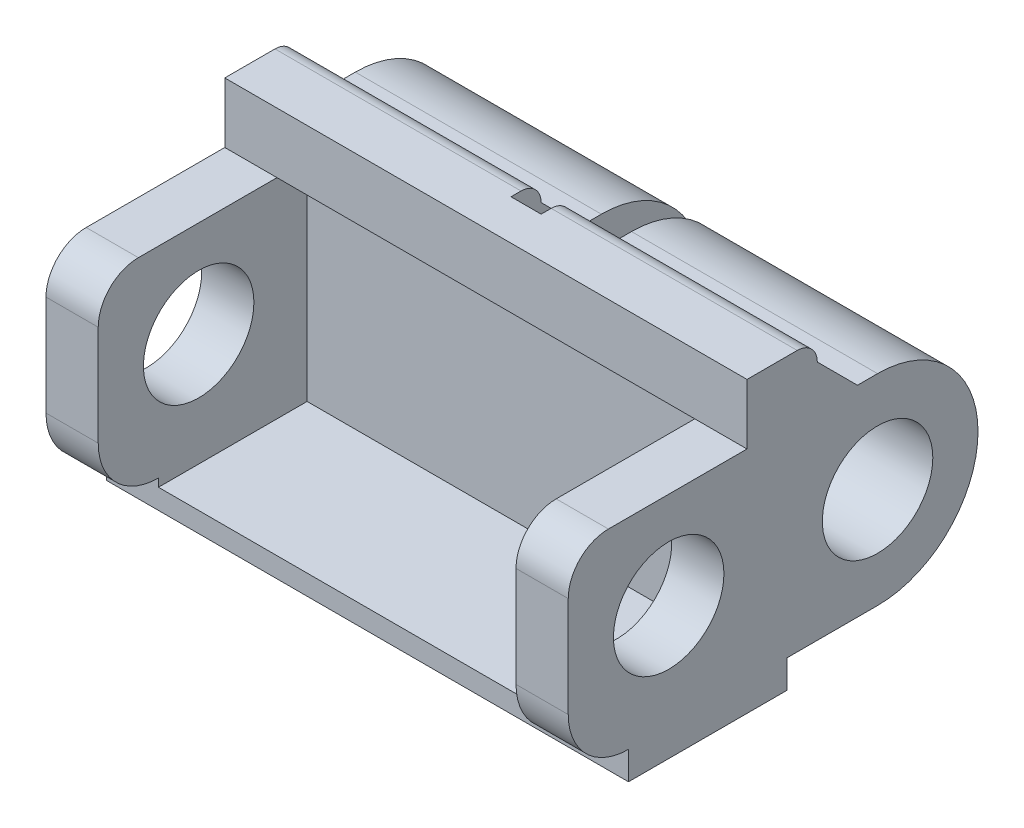
SolidWorks part; units mm, degrees
ref_plane "Front Plane" through (0, 0, 0) normal (0, 0, 1) x (1, 0, 0)
ref_plane "Top Plane" through (0, 0, 0) normal (0, 1, 0) x (1, 0, 0)
ref_plane "Right Plane" through (0, 0, 0) normal (1, 0, 0) x (0, 0, -1)
sketch "Sketch3" plane through (10, 0, 0) normal (1, 0, 0) x (0, 0, -1)
  line L1 (-42, 41.45) -> (-47, 41.45)
  line L2 (-47, 41.45) -> (-37, 41.45)
  line L4 (-44, 31.45) -> (-40, 31.45)
  line L5 (-37, 34.45) -> (-37, 41.85)
  line L6 (-37, 41.85) -> (-47, 41.85)
  line L7 (-47, 41.85) -> (-47, 34.45)
  line L8 (-44, 31.45) -> (-40, 31.45)
  line L9 (-37, 34.45) -> (-37, 41.45)
  line L11 (-47, 41.45) -> (-47, 34.45)
  circle A0 centre (-42, 36.65) radius 2.75
  arc A3 (-40, 31.45) -> (-37, 34.45) centre (-40, 34.45) ccw
  arc A4 (-47, 34.45) -> (-44, 31.45) centre (-44, 34.45) ccw
  arc A5 (-40, 31.45) -> (-37, 34.45) centre (-40, 34.45) ccw
  arc A6 (-47, 34.45) -> (-44, 31.45) centre (-44, 34.45) ccw
  circle M10 centre (-42, 36.65) radius 2.75
  line M11 (-44, 31.45) -> (-40, 31.45)
  arc M12 (-40, 31.45) -> (-37, 34.45) centre (-40, 34.45) ccw
  line M13 (-37, 34.45) -> (-37, 41.85)
  line M15 (-47, 41.85) -> (-47, 34.45)
  arc M16 (-47, 34.45) -> (-44, 31.45) centre (-44, 34.45) ccw
  dimension "D1" = 0
extrude "Boss-Extrude1" add sketch "Sketch3" along normal blind 3 contours L2 L1 M15 M16 M11 M12 M13 M10
sketch "Sketch4" plane through (-10, 0, 0) normal (-1, 0, 0) x (0, 0, 1)
  line L4 (47, 41.45) -> (37, 41.45)
  line L5 (47, 34.45) -> (47, 41.45)
  line L6 (40, 31.45) -> (44, 31.45)
  line L7 (37, 41.45) -> (37, 34.45)
  line L8 (47, 41.45) -> (37, 41.45)
  line L9 (47, 34.45) -> (47, 41.45)
  line L10 (40, 31.45) -> (44, 31.45)
  line L11 (37, 41.45) -> (37, 34.45)
  circle A1 centre (42, 36.65) radius 2.75
  circle A2 centre (42, 36.65) radius 2.75
  arc A4 (44, 31.45) -> (47, 34.45) centre (44, 34.45) ccw
  arc A5 (37, 34.45) -> (40, 31.45) centre (40, 34.45) ccw
  arc A6 (44, 31.45) -> (47, 34.45) centre (44, 34.45) ccw
  arc A7 (37, 34.45) -> (40, 31.45) centre (40, 34.45) ccw
  dimension "D1" = 0
  dimension "D2" = 0
extrude "Boss-Extrude2" add sketch "Sketch4" along normal blind 3 separate body
sketch "Sketch5" plane through (-13, 0, 0) normal (-1, 0, 0) x (0, 0, 1)
  line L0 (37, 41.45) -> (36.6, 41.45)
  line L1 (40, 31.45) -> (36.6, 31.45)
  line L2 (36.6, 41.45) -> (36.6, 31.45)
  line L3 (37, 41.45) -> (37, 34.45) construction
  line L4 (37, 41.45) -> (37, 34.45)
  arc A0 (37, 34.45) -> (40, 31.45) centre (40, 34.45) ccw construction
  arc A2 (37, 34.45) -> (40, 31.45) centre (40, 34.45) ccw
  dimension "D1" = 0.4
extrude "Boss-Extrude3" add sketch "Sketch5" against normal blind 3
sketch "Sketch6" plane through (13, 0, 0) normal (1, 0, 0) x (0, 0, -1)
  line L4 (-36.6, 31.45) -> (-36.6, 41.45)
  line L5 (-36.6, 41.45) -> (-47, 41.45)
  line L6 (-47, 41.45) -> (-47, 34.45)
  line L7 (-44, 31.45) -> (-36.6, 31.45)
  line L8 (-36.6, 31.45) -> (-36.6, 41.45)
  line L9 (-36.6, 41.45) -> (-47, 41.45)
  line L10 (-47, 41.45) -> (-47, 34.45)
  line L11 (-44, 31.45) -> (-36.6, 31.45)
  circle A0 centre (-42, 36.65) radius 2.75 construction
  arc A1 (-47, 34.45) -> (-44, 31.45) centre (-44, 34.45) ccw
  arc A2 (-47, 34.45) -> (-44, 31.45) centre (-44, 34.45) ccw
  circle A3 centre (-42, 36.65) radius 2.75
  dimension "D1" = 0
extrude "Boss-Extrude4" add sketch "Sketch6" against normal blind 3
sketch "Sketch7" plane through (-10, 0, 0) normal (1, 0, 0) x (0, 0, -1)
  line L4 (-36.6, 41.45) -> (-47, 41.45)
  line L5 (-47, 41.45) -> (-47, 34.45)
  line L6 (-44, 31.45) -> (-36.6, 31.45)
  line L7 (-36.6, 31.45) -> (-36.6, 41.45)
  line L8 (-36.6, 41.45) -> (-47, 41.45)
  line L9 (-47, 41.45) -> (-47, 34.45)
  line L10 (-44, 31.45) -> (-36.6, 31.45)
  line L11 (-36.6, 31.45) -> (-36.6, 41.45)
  arc A1 (-47, 34.45) -> (-44, 31.45) centre (-44, 34.45) ccw
  arc A2 (-47, 34.45) -> (-44, 31.45) centre (-44, 34.45) ccw
  dimension "D1" = 0
extrude "Cut-Extrude1" cut sketch "Sketch7" against normal blind 0.4
sketch "Sketch8" plane through (10, 0, 0) normal (-1, 0, 0) x (0, 0, 1)
  line L4 (47, 41.45) -> (36.6, 41.45)
  line L5 (36.6, 41.45) -> (36.6, 31.45)
  line L6 (36.6, 31.45) -> (44, 31.45)
  line L7 (47, 34.45) -> (47, 41.45)
  line L8 (47, 41.45) -> (36.6, 41.45)
  line L9 (36.6, 41.45) -> (36.6, 31.45)
  line L10 (36.6, 31.45) -> (44, 31.45)
  line L11 (47, 34.45) -> (47, 41.45)
  arc A1 (44, 31.45) -> (47, 34.45) centre (44, 34.45) ccw
  arc A2 (44, 31.45) -> (47, 34.45) centre (44, 34.45) ccw
  dimension "D1" = 0
extrude "Cut-Extrude2" cut sketch "Sketch8" against normal blind 0.4
sketch "Sketch9" plane through (13, 0, 0) normal (1, 0, 0) x (0, 0, -1)
  line L0 (-36.6, 31.45) -> (-34.3437, 31.45)
  line L1 (-36.6, 41.45) -> (-36.6, 31.45)
  line L2 (-36.6, 41.45) -> (-31.6, 41.45)
  line L4 (-31.6, 31.45) -> (-36.6, 31.45)
  line L5 (-36.6, 36.45) -> (-26.6, 36.45)
  circle A0 centre (-31.6, 36.45) radius 2.75
  circle A1 centre (-31.6, 36.45) radius 5
  line M9 (-36.6, 31.45) -> (-36.6, 41.45)
  dimension "D2" = 5.5
extrude "Boss-Extrude5" add sketch "Sketch9" against normal up to surface (26 mm away) contours L5 A1 A0 | L5 A1 A0 | A1 L2 L1 | A1 L0 L4 M9 up to face at (-13, 35.9257, 42.3643)
ref_plane "Plane1" through (0, 0, 26.6) normal (0, 0, 1) x (1, 0, 0)
sketch "Sketch11" plane through (0, 0, 26.6) normal (0, 0, 1) x (1, 0, 0)
  line L0 (-0.75, 41.85) -> (0.75, 41.85)
  line L1 (0.75, 41.85) -> (0.75, 31.45)
  line L2 (-10.4, 31.45) -> (10.4, 31.45) construction
  line L3 (0.75, 34.45) -> (0.75, 31.45) construction
  line L4 (0.75, 31.45) -> (-0.75, 31.45)
  line L5 (-0.75, 31.45) -> (-0.75, 34.45) construction
  line L6 (-0.75, 31.45) -> (-0.75, 41.85)
extrude "Cut-Extrude4" cut sketch "Sketch11" along normal mid plane 19
ref_plane "Plane2" through (0, 31.05, 0) normal (0, -1, 0) x (-1, 0, 0)
sketch "Sketch13" plane through (0, 31.05, 0) normal (0, -1, 0) x (-1, 0, 0)
  line L0 (-10.4, -36.6) -> (-13, -36.6)
  line L1 (-13, -44) -> (-13, -31.6) construction
  line L2 (-13, -36.6) -> (13, -36.6)
  line L3 (13, -31.6) -> (13, -44) construction
  line L4 (13, -36.6) -> (13, -41.6)
  line L5 (13, -41.6) -> (-13, -41.6)
  line L6 (-13, -41.6) -> (-13, -36.6)
  line L7 (-0.75, -36.1) -> (-0.75, -36.6)
  line L8 (-0.75, -36.1) -> (-13, -36.1)
  line L9 (-13, -36.1) -> (-13, -36.6)
  line L10 (-0.75, -36.1) -> (13, -36.1)
  line L11 (13, -36.1) -> (13, -36.6)
  dimension "D1" = 5
extrude "Boss-Extrude6" add sketch "Sketch13" along normal blind 1 separate body contours L6 L5 L4 L2 L0 | L11 L10 L7 L2 | L8 L9 L0 L2 L7
sketch "Sketch14" plane through (0, 31.45, 0) normal (0, -1, 0) x (1, 0, 0)
  line L0 (10.4, 41.6) -> (13, 41.6)
  line L1 (-13, 41.6) -> (13, 41.6) construction
  line L2 (10.4, 36.6) -> (10.4, 44) construction
  line L3 (13, 41.6) -> (13, 36.1)
  line L4 (13, 36.1) -> (-13, 36.1)
  line L5 (-13, 36.1) -> (-13, 41.6)
  line L6 (-13, 41.6) -> (-10.4, 41.6)
  line L7 (-10.4, 44) -> (-10.4, 36.6) construction
  line L8 (10.4, 41.6) -> (10.4, 36.6)
  line L9 (10.4, 36.6) -> (-10.4, 36.6)
  line L10 (-10.4, 36.6) -> (-10.4, 41.6)
extrude "Boss-Extrude7" add sketch "Sketch14" along normal blind 1
sketch "Sketch15" plane through (0, 41.45, 0) normal (0, 1, 0) x (1, 0, 0)
  line L0 (10.4, -36.6) -> (13, -36.6)
  line L1 (13, -47) -> (13, -31.6) construction
  line L2 (13, -36.6) -> (-13, -36.6)
  line L3 (-13, -47) -> (-13, -31.6) construction
  line L4 (-13, -36.6) -> (-13, -34.6)
  line L5 (-13, -34.6) -> (13, -34.6)
  line L6 (13, -34.6) -> (13, -36.6)
  line M2 (-0.75, -36.1) -> (-0.75, -31.6)
  line M4 (-13, -31.6) -> (-13, -47)
  line M7 (-10.4, -36.6) -> (10.4, -36.6)
  line M10 (13, -47) -> (13, -31.6)
  line M12 (0.75, -31.6) -> (0.75, -36.1)
  line M13 (0.75, -36.1) -> (-0.75, -36.1)
  dimension "D1" = 2
extrude "Boss-Extrude8" add sketch "Sketch15" along normal blind 3 contours L5 L2 L0 M4 M7 M10 M12 M13 M2
chamfer "Chamfer1" distance 2 angle 45 1 edges at (-6.875, 41.45, 34.6)
fillet "Fillet1" radius 1 2 edges at (-6.875, 44.45, 34.6) (6.875, 44.45, 34.6)
sketch "Sketch16" plane through (0, 0, 36.6) normal (0, 0, 1) x (1, 0, 0)
  line L1 (-13, 44.45) -> (13, 44.45)
  line L2 (-13, 44.45) -> (-13, 41.45)
  line L3 (-13, 41.45) -> (13, 41.45)
  line L4 (13, 44.45) -> (13, 41.45)
extrude "Boss-Extrude9" add sketch "Sketch16" along normal blind 1
fillet "Fillet2" radius 2 2 edges at (11.7, 41.45, 47) (-11.7, 41.45, 47)
sketch "Sketch17" plane through (0, 0, 41.6) normal (0, 0, 1) x (1, 0, 0)
  line L8 (10.4, 31.05) -> (-10.4, 31.05)
  line L9 (-10.4, 31.05) -> (-10.4, 31.45)
  line L10 (-10.4, 31.45) -> (-13, 31.45)
  line L11 (-13, 31.45) -> (-13, 30.05)
  line L12 (-13, 30.05) -> (13, 30.05)
  line L13 (13, 30.05) -> (13, 31.45)
  line L14 (13, 31.45) -> (10.4, 31.45)
  line L15 (10.4, 31.45) -> (10.4, 31.05)
  line L16 (10.4, 31.05) -> (-10.4, 31.05)
  line L17 (-10.4, 31.05) -> (-10.4, 31.45)
  line L18 (-10.4, 31.45) -> (-13, 31.45)
  line L19 (-13, 31.45) -> (-13, 30.05)
  line L20 (-13, 30.05) -> (13, 30.05)
  line L21 (13, 30.05) -> (13, 31.45)
  line L22 (13, 31.45) -> (10.4, 31.45)
  line L23 (10.4, 31.45) -> (10.4, 31.05)
  dimension "D1" = 0
extrude "Boss-Extrude11" add sketch "Sketch17" along normal up to vertex (2.4 mm away)
sketch "Sketch18" plane through (0, 0, 37.6) normal (0, 0, 1) x (1, 0, 0)
  line L6 (-13, 44.45) -> (-13, 41.45)
  line L7 (-13, 41.45) -> (-10.4, 41.45)
  line L8 (-10.4, 41.45) -> (10.4, 41.45)
  line L9 (10.4, 41.45) -> (13, 41.45)
  line L10 (13, 41.45) -> (13, 44.45)
  line L11 (13, 44.45) -> (-13, 44.45)
  line L12 (-13, 44.45) -> (-13, 41.45)
  line L13 (-13, 41.45) -> (-10.4, 41.45)
  line L14 (-10.4, 41.45) -> (10.4, 41.45)
  line L15 (10.4, 41.45) -> (13, 41.45)
  line L16 (13, 41.45) -> (13, 44.45)
  line L17 (13, 44.45) -> (-13, 44.45)
  dimension "D1" = 0
extrude "Boss-Extrude12" add sketch "Sketch18" along normal blind 1
sketch "Sketch19" plane through (0, 0, 38.6) normal (0, 0, 1) x (1, 0, 0)
  line L6 (13, 44.45) -> (-13, 44.45)
  line L7 (-13, 44.45) -> (-13, 41.45)
  line L8 (-13, 41.45) -> (-10.4, 41.45)
  line L9 (-10.4, 41.45) -> (10.4, 41.45)
  line L10 (10.4, 41.45) -> (13, 41.45)
  line L11 (13, 41.45) -> (13, 44.45)
  line L12 (13, 44.45) -> (-13, 44.45)
  line L13 (-13, 44.45) -> (-13, 41.45)
  line L14 (-13, 41.45) -> (-10.4, 41.45)
  line L15 (-10.4, 41.45) -> (10.4, 41.45)
  line L16 (10.4, 41.45) -> (13, 41.45)
  line L17 (13, 41.45) -> (13, 44.45)
  dimension "D1" = 0
extrude "Cut-Extrude5" cut sketch "Sketch19" against normal blind 0.5
